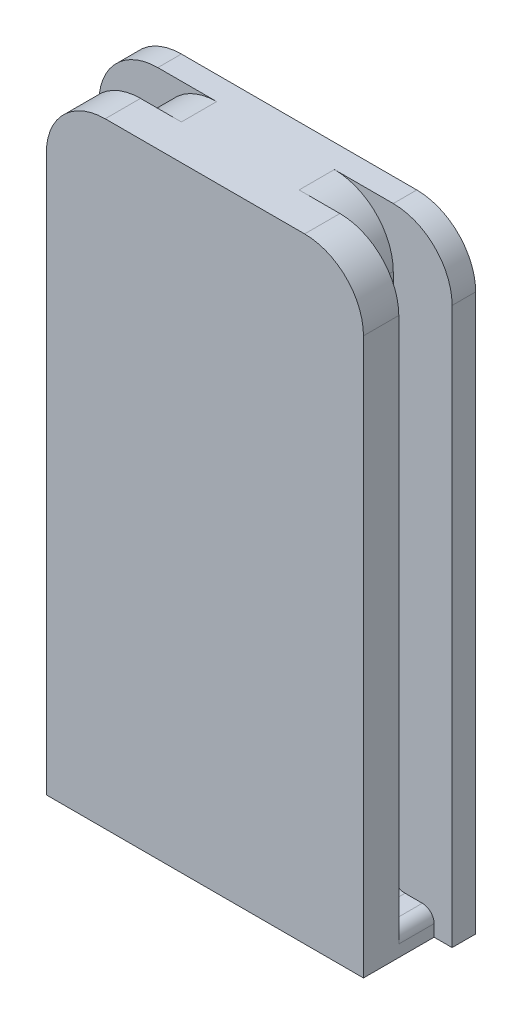
SolidWorks part; units mm, degrees
ref_plane "Front" through (0, 0, 0) normal (0, 0, 1) x (1, 0, 0)
ref_plane "Top" through (0, 0, 0) normal (0, 1, 0) x (1, 0, 0)
ref_plane "Right" through (0, 0, 0) normal (1, 0, 0) x (0, 0, -1)
sketch "Sketch1" plane through (0, 0, 0) normal (0, 1, 0) x (1, 0, 0)
  line L0 (13.4702, 0) -> (-13.4702, 0)
  line L1 (-13.4702, 0) -> (-13.4702, 3)
  line L2 (-13.4702, 3) -> (-10, 3)
  line L3 (-10, 3) -> (-10, 6)
  line L4 (-10, 6) -> (-15, 6)
  line L5 (-15, 6) -> (-15, 8)
  line L6 (-15, 8) -> (15, 8)
  line L7 (0, 0) -> (0, 20) construction
  line L8 (15, 6) -> (15, 8)
  line L9 (10, 6) -> (15, 6)
  line L10 (10, 3) -> (10, 6)
  line L11 (13.4702, 3) -> (10, 3)
  line L12 (13.4702, 0) -> (13.4702, 3)
  point P12 (0, 8)
  dimension "D1" = 3
  dimension "D2" = 3
  dimension "D3" = 2
  dimension "D4" = 30
  dimension "D5" = 20
extrude "Boss-Extrude1" add sketch "Sketch1" along normal blind 52.2438
sketch "Sketch2" plane through (0, 0, 0) normal (0, -1, 0) x (1, 0, 0)
  line L0 (13.4702, 0) -> (13.4702, -3) construction
  line L1 (-13.4702, -7.0252) -> (13.4702, -7.0252)
  line L2 (-13.4702, -7.0252) -> (-13.4702, -1.5)
  line L3 (-13.4702, -1.5) -> (13.4702, -1.5)
  line L4 (13.4702, -7.0252) -> (13.4702, -1.5)
  line L5 (-13.4702, -7.0252) -> (13.4702, -1.5) construction
  line L6 (-13.4702, -1.5) -> (13.4702, -7.0252) construction
  point P0 (0, -4.2626)
extrude "Boss-Extrude2" add sketch "Sketch2" against normal blind 2
fillet "Fillet1" radius 5 4 edges at (10, 52.2438, -4.5) (-10, 52.2438, -4.5) (-15, 52.2438, -7) (15, 52.2438, -7)
fillet "Fillet3" radius 1 4 edges at (13.4702, 2, -4.5) (10, 2, -4.5) (-13.4702, 2, -4.5) (-10, 2, -4.5)
fillet "Fillet4" radius 5 2 edges at (-13.4702, 52.2438, -1.5) (13.4702, 52.2438, -1.5)
sketch "Sketch3" plane through (0, 0, -8) normal (0, 0, -1) x (-1, 0, 0)
  circle A0 centre (0, 32) radius 3.5081
  dimension "D1" = 32
extrude "Boss-Extrude3" add sketch "Sketch3" along normal blind 2
fillet "Fillet5" radius 5 1 edges at (3.5081, 32, -8)
fillet "Fillet6" radius 5 1 edges at (-3.5081, 32, -10)
